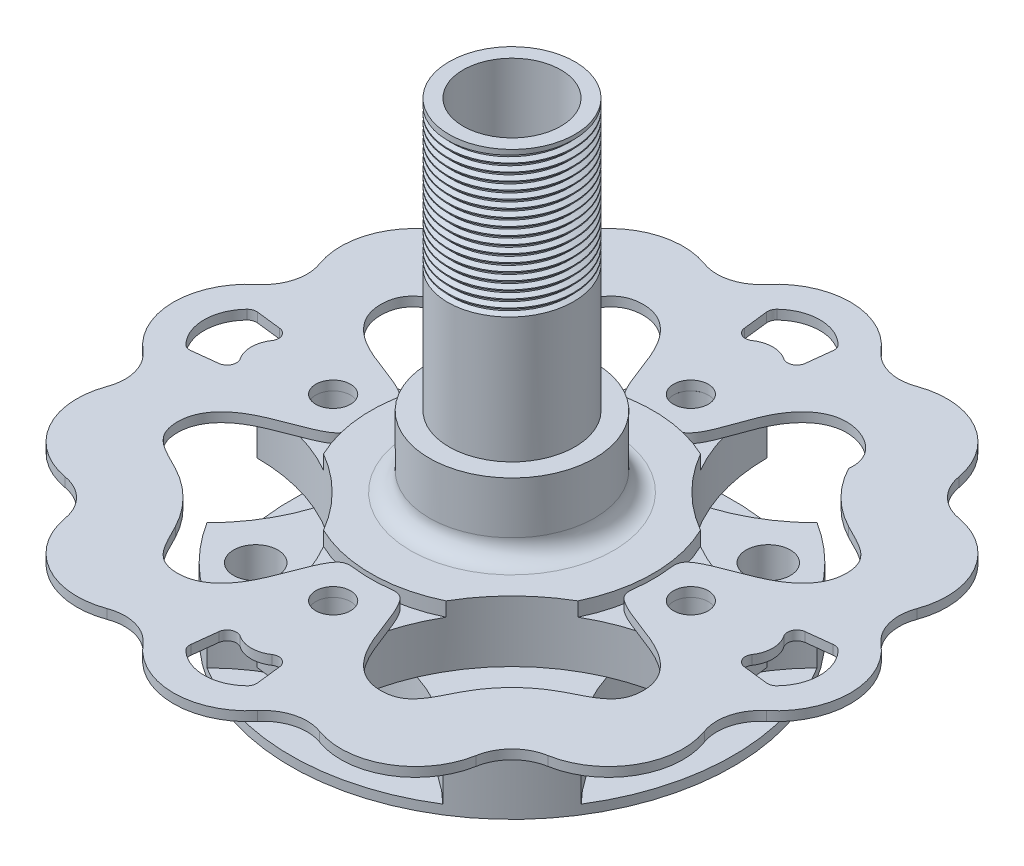
SolidWorks part; units mm, degrees
other "Camera1"
ref_plane "Front Plane" through (0, 0, 0) normal (0, 0, 1) x (1, 0, 0)
ref_plane "Top Plane" through (0, 0, 0) normal (0, 1, 0) x (1, 0, 0)
ref_plane "Right Plane" through (0, 0, 0) normal (1, 0, 0) x (0, 0, -1)
sketch "Sketch1" plane through (0, 0, 0) normal (0, 1, 0) x (1, 0, 0)
  line L0 (-91.3384, 0) -> (0, 0) construction
  line L1 (-79.1014, 45.6692) -> (0, 0) construction
  line L2 (-45.6692, 79.1014) -> (0, 0) construction
  line L3 (0, 91.3384) -> (0, 0) construction
  line L4 (-58.7488, 58.7488) -> (0, 0) construction
  line L5 (-77.6512, 8.9971) -> (-70.888, 8.2135)
  line L9 (0, 91.3384) -> (0, 0) construction
  line L10 (-8.9971, 77.6512) -> (-8.2135, 70.888)
  line L11 (8.9971, 77.6512) -> (8.2135, 70.888)
  line L12 (77.6512, 8.9971) -> (70.888, 8.2135)
  line L13 (0, 91.3384) -> (0, 0) construction
  line L16 (45.6692, 79.1014) -> (0, 0) construction
  line L17 (79.1014, 45.6692) -> (0, 0) construction
  line L18 (91.3384, 0) -> (0, 0) construction
  line L19 (58.7488, 58.7488) -> (0, 0) construction
  line L20 (91.3384, 0) -> (0, 0) construction
  line L23 (0, 91.3384) -> (0, 0) construction
  line L24 (77.6512, -8.9971) -> (70.888, -8.2135)
  line L25 (8.9971, -77.6512) -> (8.2135, -70.888)
  line L26 (-91.3384, 0) -> (0, 0) construction
  line L27 (91.3384, 0) -> (0, 0) construction
  line L28 (77.6512, -8.9971) -> (70.888, -8.2135) [skipped]
  line L30 (-8.9971, -77.6512) -> (-8.2135, -70.888) [skipped]
  line L32 (79.1014, -45.6692) -> (0, 0) construction
  line L33 (45.6692, -79.1014) -> (0, 0) construction
  line L34 (0, -91.3384) -> (0, 0) construction
  line L35 (58.7488, -58.7488) -> (0, 0) construction
  line L36 (0, -91.3384) -> (0, 0) construction
  line L37 (-45.6692, -79.1014) -> (0, 0) construction
  line L38 (-79.1014, -45.6692) -> (0, 0) construction
  line L39 (-58.7488, -58.7488) -> (0, 0) construction
  line L40 (8.9971, 77.6512) -> (8.2135, 70.888) [skipped]
  line L41 (45.6692, 79.1014) -> (0, 0) construction
  line L42 (79.1014, 45.6692) -> (0, 0) construction
  line L43 (58.7488, 58.7488) -> (0, 0) construction
  line L45 (91.3384, 0) -> (0, 0) construction
  line L46 (91.3384, 0) -> (0, 0) construction
  line L47 (79.1014, -45.6692) -> (0, 0) construction
  line L48 (45.6692, -79.1014) -> (0, 0) construction
  line L49 (0, -91.3384) -> (0, 0) construction
  line L50 (58.7488, -58.7488) -> (0, 0) construction
  line L51 (0, -91.3384) -> (0, 0) construction
  line L52 (91.3384, 0) -> (0, 0) construction
  line L53 (-8.9971, -77.6512) -> (-8.2135, -70.888)
  line L54 (-77.6512, -8.9971) -> (-70.888, -8.2135)
  line L55 (0, -91.3384) -> (0, 0) construction
  line L56 (-45.6692, -79.1014) -> (0, 0) construction
  line L57 (-79.1014, -45.6692) -> (0, 0) construction
  line L58 (-91.3384, 0) -> (0, 0) construction
  line L59 (-58.7488, -58.7488) -> (0, 0) construction
  line L60 (-91.3384, 0) -> (0, 0) construction
  line L61 (0, -91.3384) -> (0, 0) construction
  arc A0 (-83.0834, 0) -> (0, 83.0834) centre (0, 0) cw construction
  arc A2 (-91.3384, 0) -> (-84.1072, 15.4663) centre (-71.1829, 0) cw
  arc A3 (-84.1072, 15.4663) -> (-80.5721, 28.6594) centre (-91.7199, 24.5763) ccw
  arc A4 (-80.5721, 28.6594) -> (-65.1058, 55.4478) centre (-61.6462, 35.5915) cw
  arc A5 (-65.1058, 55.4478) -> (-55.4478, 65.1058) centre (-67.1436, 67.1436) ccw
  arc A6 (-55.4478, 65.1058) -> (-28.6594, 80.5721) centre (-35.5915, 61.6462) cw
  arc A7 (-28.6594, 80.5721) -> (-15.4663, 84.1072) centre (-24.5763, 91.7199) ccw
  arc A8 (-15.4663, 84.1072) -> (0, 91.3384) centre (0, 71.1829) cw
  arc A9 (-61.618, 35.4294) -> (-35.4294, 61.618) centre (-67.1436, 67.1436) ccw
  arc A10 (-38.1, 0) -> (-37.7962, 4.8015) centre (0, 0) cw
  arc A11 (-83.0834, 0) -> (-79.7781, 8.2307) centre (-71.1829, 0) cw
  arc A12 (-69.0761, 4.2678) -> (-70.3834, 0) centre (-62.7634, 0) ccw
  arc A14 (-83.0834, 0) -> (-78.8139, 9.1318) centre (-71.1829, 0) cw construction
  arc A15 (-77.6512, 8.9971) -> (-79.7781, 8.2307) centre (-77.9435, 6.474) ccw
  arc A16 (-69.0761, 4.2678) -> (-70.888, 8.2135) centre (-71.1804, 5.6904) ccw
  circle A17 centre (-48.26, 0) radius 4.699
  arc A29 (0, 38.1) -> (-4.8015, 37.7962) centre (0, 0) ccw
  arc A30 (-4.2678, 69.0761) -> (0, 70.3834) centre (0, 62.7634) cw
  arc A36 (-4.2678, 69.0761) -> (-8.2135, 70.888) centre (-5.6904, 71.1804) cw
  arc A41 (-8.9971, 77.6512) -> (-8.2307, 79.7781) centre (-6.474, 77.9435) cw
  arc A42 (0, 83.0834) -> (-8.2307, 79.7781) centre (0, 71.1829) ccw
  arc A50 (0, 91.3384) -> (15.4663, 84.1072) centre (0, 71.1829) cw
  arc A51 (15.4663, 84.1072) -> (28.6594, 80.5721) centre (24.5763, 91.7199) ccw
  arc A57 (28.6594, 80.5721) -> (55.4478, 65.1058) centre (35.5915, 61.6462) cw
  arc A62 (55.4478, 65.1058) -> (65.1058, 55.4478) centre (67.1436, 67.1436) ccw
  arc A63 (65.1058, 55.4478) -> (80.5721, 28.6594) centre (61.6462, 35.5915) cw
  arc A71 (80.5721, 28.6594) -> (84.1072, 15.4663) centre (91.7199, 24.5763) ccw
  arc A72 (84.1072, 15.4663) -> (91.3384, 0) centre (71.1829, 0) cw
  arc A78 (-38.1, 0) -> (-37.7962, -4.8015) centre (0, 0) ccw
  arc A81 (-69.0761, -4.2678) -> (-70.3834, 0) centre (-62.7634, 0) cw
  arc A83 (35.4294, 61.618) -> (61.618, 35.4294) centre (67.1436, 67.1436) ccw
  arc A84 (0, 38.1) -> (4.8015, 37.7962) centre (0, 0) cw
  arc A85 (91.3384, 0) -> (84.1072, -15.4663) centre (71.1829, 0) cw [skipped]
  arc A86 (84.1072, -15.4663) -> (80.5721, -28.6594) centre (91.7199, -24.5763) ccw [skipped]
  arc A87 (80.5721, -28.6594) -> (65.1058, -55.4478) centre (61.6462, -35.5915) cw [skipped]
  arc A88 (65.1058, -55.4478) -> (55.4478, -65.1058) centre (67.1436, -67.1436) ccw [skipped]
  arc A89 (55.4478, -65.1058) -> (28.6594, -80.5721) centre (35.5915, -61.6462) cw [skipped]
  arc A90 (28.6594, -80.5721) -> (15.4663, -84.1072) centre (24.5763, -91.7199) ccw [skipped]
  arc A91 (15.4663, -84.1072) -> (0, -91.3384) centre (0, -71.1829) cw [skipped]
  arc A92 (61.618, -35.4294) -> (35.4294, -61.618) centre (67.1436, -67.1436) ccw [skipped]
  arc A93 (83.0834, 0) -> (79.7781, -8.2307) centre (71.1829, 0) cw [skipped]
  arc A95 (77.6512, -8.9971) -> (79.7781, -8.2307) centre (77.9435, -6.474) ccw [skipped]
  arc A96 (69.0761, -4.2678) -> (70.888, -8.2135) centre (71.1804, -5.6904) ccw [skipped]
  arc A102 (0, -91.3384) -> (-15.4663, -84.1072) centre (0, -71.1829) cw [skipped]
  arc A103 (-15.4663, -84.1072) -> (-28.6594, -80.5721) centre (-24.5763, -91.7199) ccw [skipped]
  arc A104 (-28.6594, -80.5721) -> (-55.4478, -65.1058) centre (-35.5915, -61.6462) cw [skipped]
  arc A105 (-55.4478, -65.1058) -> (-65.1058, -55.4478) centre (-67.1436, -67.1436) ccw [skipped]
  arc A106 (-65.1058, -55.4478) -> (-80.5721, -28.6594) centre (-61.6462, -35.5915) cw [skipped]
  arc A107 (-80.5721, -28.6594) -> (-84.1072, -15.4663) centre (-91.7199, -24.5763) ccw [skipped]
  arc A108 (-84.1072, -15.4663) -> (-91.3384, 0) centre (-71.1829, 0) cw [skipped]
  arc A109 (-35.4294, -61.618) -> (-61.618, -35.4294) centre (-67.1436, -67.1436) ccw [skipped]
  arc A110 (0, -38.1) -> (-4.8015, -37.7962) centre (0, 0) cw [skipped]
  arc A111 (0, -83.0834) -> (-8.2307, -79.7781) centre (0, -71.1829) cw [skipped]
  arc A112 (-4.2678, -69.0761) -> (0, -70.3834) centre (0, -62.7634) ccw [skipped]
  arc A114 (-8.9971, -77.6512) -> (-8.2307, -79.7781) centre (-6.474, -77.9435) ccw [skipped]
  arc A115 (-4.2678, -69.0761) -> (-8.2135, -70.888) centre (-5.6904, -71.1804) ccw [skipped]
  arc A119 (83.0834, 0) -> (0, -83.0834) centre (0, 0) cw construction
  arc A121 (0, -83.0834) -> (-83.0834, 0) centre (0, 0) cw construction
  arc A123 (0, 91.3384) -> (15.4663, 84.1072) centre (0, 71.1829) cw [skipped]
  arc A124 (15.4663, 84.1072) -> (28.6594, 80.5721) centre (24.5763, 91.7199) ccw [skipped]
  arc A125 (28.6594, 80.5721) -> (55.4478, 65.1058) centre (35.5915, 61.6462) cw [skipped]
  arc A126 (55.4478, 65.1058) -> (65.1058, 55.4478) centre (67.1436, 67.1436) ccw [skipped]
  arc A127 (65.1058, 55.4478) -> (80.5721, 28.6594) centre (61.6462, 35.5915) cw [skipped]
  arc A128 (80.5721, 28.6594) -> (84.1072, 15.4663) centre (91.7199, 24.5763) ccw [skipped]
  arc A129 (84.1072, 15.4663) -> (91.3384, 0) centre (71.1829, 0) cw [skipped]
  arc A130 (35.4294, 61.618) -> (61.618, 35.4294) centre (67.1436, 67.1436) ccw [skipped]
  arc A131 (0, 38.1) -> (4.8015, 37.7962) centre (0, 0) cw [skipped]
  arc A132 (0, 83.0834) -> (8.2307, 79.7781) centre (0, 71.1829) cw [skipped]
  arc A133 (4.2678, 69.0761) -> (0, 70.3834) centre (0, 62.7634) ccw [skipped]
  arc A135 (8.9971, 77.6512) -> (8.2307, 79.7781) centre (6.474, 77.9435) ccw [skipped]
  arc A136 (4.2678, 69.0761) -> (8.2135, 70.888) centre (5.6904, 71.1804) ccw [skipped]
  arc A138 (0, 83.0834) -> (83.0834, 0) centre (0, 0) cw construction
  arc A144 (38.1, 0) -> (37.7962, -4.8015) centre (0, 0) cw [skipped]
  arc A145 (69.0761, -4.2678) -> (70.3834, 0) centre (62.7634, 0) ccw [skipped]
  arc A146 (0, 83.0834) -> (8.2307, 79.7781) centre (0, 71.1829) cw
  arc A147 (4.2678, 69.0761) -> (0, 70.3834) centre (0, 62.7634) ccw
  arc A148 (8.9971, 77.6512) -> (8.2307, 79.7781) centre (6.474, 77.9435) ccw
  arc A149 (4.2678, 69.0761) -> (8.2135, 70.888) centre (5.6904, 71.1804) ccw
  circle A150 centre (0, 48.26) radius 4.699
  arc A151 (38.1, 0) -> (37.7962, 4.8015) centre (0, 0) ccw
  arc A152 (69.0761, 4.2678) -> (70.3834, 0) centre (62.7634, 0) cw
  arc A153 (69.0761, 4.2678) -> (70.888, 8.2135) centre (71.1804, 5.6904) cw
  arc A154 (77.6512, 8.9971) -> (79.7781, 8.2307) centre (77.9435, 6.474) cw
  arc A155 (83.0834, 0) -> (79.7781, 8.2307) centre (71.1829, 0) ccw
  arc A156 (0, 38.1) -> (-4.8015, 37.7962) centre (0, 0) ccw
  arc A157 (-4.2678, 69.0761) -> (0, 70.3834) centre (0, 62.7634) cw
  arc A158 (0, 83.0834) -> (83.0834, 0) centre (0, 0) cw construction
  arc A159 (0, 91.3384) -> (91.3384, 0) centre (0, 0) cw construction
  arc A160 (91.3384, 0) -> (84.1072, -15.4663) centre (71.1829, 0) cw
  arc A161 (84.1072, -15.4663) -> (80.5721, -28.6594) centre (91.7199, -24.5763) ccw
  arc A162 (80.5721, -28.6594) -> (65.1058, -55.4478) centre (61.6462, -35.5915) cw
  arc A163 (65.1058, -55.4478) -> (55.4478, -65.1058) centre (67.1436, -67.1436) ccw
  arc A164 (55.4478, -65.1058) -> (28.6594, -80.5721) centre (35.5915, -61.6462) cw
  arc A165 (28.6594, -80.5721) -> (15.4663, -84.1072) centre (24.5763, -91.7199) ccw
  arc A166 (15.4663, -84.1072) -> (0, -91.3384) centre (0, -71.1829) cw
  arc A167 (61.618, -35.4294) -> (35.4294, -61.618) centre (67.1436, -67.1436) ccw
  arc A168 (38.1, 0) -> (37.7962, -4.8015) centre (0, 0) cw
  arc A169 (83.0834, 0) -> (79.7781, -8.2307) centre (71.1829, 0) cw
  arc A170 (69.0761, -4.2678) -> (70.3834, 0) centre (62.7634, 0) ccw
  arc A171 (77.6512, -8.9971) -> (79.7781, -8.2307) centre (77.9435, -6.474) ccw
  arc A172 (69.0761, -4.2678) -> (70.888, -8.2135) centre (71.1804, -5.6904) ccw
  circle A173 centre (48.26, 0) radius 4.699
  arc A174 (0, -38.1) -> (4.8015, -37.7962) centre (0, 0) ccw
  arc A175 (4.2678, -69.0761) -> (0, -70.3834) centre (0, -62.7634) cw
  arc A176 (4.2678, -69.0761) -> (8.2135, -70.888) centre (5.6904, -71.1804) cw
  arc A177 (8.9971, -77.6512) -> (8.2307, -79.7781) centre (6.474, -77.9435) cw
  arc A178 (0, -83.0834) -> (8.2307, -79.7781) centre (0, -71.1829) ccw
  arc A179 (38.1, 0) -> (37.7962, 4.8015) centre (0, 0) ccw
  arc A180 (69.0761, 4.2678) -> (70.3834, 0) centre (62.7634, 0) cw
  arc A181 (83.0834, 0) -> (0, -83.0834) centre (0, 0) cw construction
  arc A182 (91.3384, 0) -> (0, -91.3384) centre (0, 0) cw construction
  arc A183 (0, -91.3384) -> (-15.4663, -84.1072) centre (0, -71.1829) cw
  arc A184 (-15.4663, -84.1072) -> (-28.6594, -80.5721) centre (-24.5763, -91.7199) ccw
  arc A185 (-28.6594, -80.5721) -> (-55.4478, -65.1058) centre (-35.5915, -61.6462) cw
  arc A186 (-55.4478, -65.1058) -> (-65.1058, -55.4478) centre (-67.1436, -67.1436) ccw
  arc A187 (-65.1058, -55.4478) -> (-80.5721, -28.6594) centre (-61.6462, -35.5915) cw
  arc A188 (-80.5721, -28.6594) -> (-84.1072, -15.4663) centre (-91.7199, -24.5763) ccw
  arc A189 (-84.1072, -15.4663) -> (-91.3384, 0) centre (-71.1829, 0) cw
  arc A190 (-35.4294, -61.618) -> (-61.618, -35.4294) centre (-67.1436, -67.1436) ccw
  arc A191 (0, -38.1) -> (-4.8015, -37.7962) centre (0, 0) cw
  arc A192 (0, -83.0834) -> (-8.2307, -79.7781) centre (0, -71.1829) cw
  arc A193 (-4.2678, -69.0761) -> (0, -70.3834) centre (0, -62.7634) ccw
  arc A194 (-8.9971, -77.6512) -> (-8.2307, -79.7781) centre (-6.474, -77.9435) ccw
  arc A195 (-4.2678, -69.0761) -> (-8.2135, -70.888) centre (-5.6904, -71.1804) ccw
  circle A196 centre (0, -48.26) radius 4.699
  arc A197 (-38.1, 0) -> (-37.7962, -4.8015) centre (0, 0) ccw
  arc A198 (-69.0761, -4.2678) -> (-70.3834, 0) centre (-62.7634, 0) cw
  arc A199 (-69.0761, -4.2678) -> (-70.888, -8.2135) centre (-71.1804, -5.6904) cw
  arc A200 (-77.6512, -8.9971) -> (-79.7781, -8.2307) centre (-77.9435, -6.474) cw
  arc A201 (-83.0834, 0) -> (-79.7781, -8.2307) centre (-71.1829, 0) ccw
  arc A202 (0, -38.1) -> (4.8015, -37.7962) centre (0, 0) ccw
  arc A203 (4.2678, -69.0761) -> (0, -70.3834) centre (0, -62.7634) cw
  arc A204 (0, -83.0834) -> (-83.0834, 0) centre (0, 0) cw construction
  arc A205 (0, -91.3384) -> (-91.3384, 0) centre (0, 0) cw construction
  spline S0 degree 3 poles (-52.2384, 38.6101) (-57.1023, 36.0693) (-62.2546, 34.2055) (-63.3566, 23.0387) (-56.4818, 14.6017) (-38.7119, 10.4134) (-37.5569, 6.6856) (-37.7962, 4.8015) knots 0 0 0 0 0.284167 0.347787 0.6362 0.911955 1 1 1 1
  spline S1 degree 3 poles (-38.6101, 52.2384) (-36.0693, 57.1023) (-34.2055, 62.2546) (-23.0387, 63.3566) (-14.6017, 56.4818) (-10.4134, 38.7119) (-6.6856, 37.5569) (-4.8015, 37.7962) knots 0 0 0 0 0.284167 0.347787 0.6362 0.911955 1 1 1 1
  spline S2 degree 3 poles (38.6101, 52.2384) (39.4918, 58.7472) (27.2418, 66.5399) (13.0177, 55.4204) (10.7787, 36.3141) (4.8015, 37.7962) knots 0 0 0 0 0.347787 0.6362 1 1 1 1
  spline S3 degree 3 poles (52.2384, 38.6101) (57.1023, 36.0693) (62.2546, 34.2055) (63.3566, 23.0387) (56.4818, 14.6017) (38.7119, 10.4134) (37.5569, 6.6856) (37.7962, 4.8015) knots 0 0 0 0 0.284167 0.347787 0.6362 0.911955 1 1 1 1
  spline S4 degree 3 poles (52.2384, -38.6101) (57.1023, -36.0693) (62.2546, -34.2055) (63.3566, -23.0387) (56.4818, -14.6017) (38.7119, -10.4134) (37.5569, -6.6856) (37.7962, -4.8015) knots 0 0 0 0 0.284167 0.347787 0.6362 0.911955 1 1 1 1
  spline S5 degree 3 poles (38.6101, -52.2384) (36.0693, -57.1023) (34.2055, -62.2546) (23.0387, -63.3566) (14.6017, -56.4818) (10.4134, -38.7119) (6.6856, -37.5569) (4.8015, -37.7962) knots 0 0 0 0 0.284167 0.347787 0.6362 0.911955 1 1 1 1
  spline S6 degree 3 poles (-38.6101, -52.2384) (-36.0693, -57.1023) (-34.2055, -62.2546) (-23.0387, -63.3566) (-14.6017, -56.4818) (-10.4134, -38.7119) (-6.6856, -37.5569) (-4.8015, -37.7962) knots 0 0 0 0 0.284167 0.347787 0.6362 0.911955 1 1 1 1
  spline S7 degree 3 poles (-52.2384, -38.6101) (-57.1023, -36.0693) (-62.2546, -34.2055) (-63.3566, -23.0387) (-56.4818, -14.6017) (-38.7119, -10.4134) (-37.5569, -6.6856) (-37.7962, -4.8015) knots 0 0 0 0 0.284167 0.347787 0.6362 0.911955 1 1 1 1
  point P26 (0, 0)
  point P27 (-79.1014, 45.6692)
  point P32 (-45.6692, 79.1014)
  point P89 (0, 0)
  point P90 (0, 0)
  point P124 (0, 0)
  point P125 (0, 0)
  point P127 (0, 0)
  point P131 (0, 0)
  point P146 (0, 0)
  point P156 (0, 0)
  point P190 (0, 0)
  point P191 (0, 0)
  point P193 (0, 0)
  point P197 (0, 0)
  point P203 (0, 0)
  point P223 (0, 0)
  point P237 (0, 0)
  point P454 (0, 0)
  point P456 (0, 0)
  point P458 (0, 0)
  point P462 (0, 0)
  point P463 (0, 0)
  dimension "D5" = 10.16
  dimension "D8" = 7.62
  dimension "D11" = 2.54
  dimension "D12" = 2.54
  dimension "D3" = 9.398
  dimension "D7" = 4
  dimension "D4" = 20.32
  dimension "D6" = 8.255
  dimension "D13" = 4
extrude "Boss-Extrude2" add sketch "Sketch1" along normal blind 2.54 contours L10 A8 A7 A6 A5 A4 A3 A2 A11 A15 L5 A16 A12 A81 region at (-87.101, 0, -7.4424)
sketch "Sketch4" plane through (0, 0, 0) normal (0, -1, 0) x (1, 0, 0)
  line L0 (-58.858, 9.9314) -> (-58.858, -9.9314) construction
  line L1 (9.9314, 58.858) -> (-9.9314, 58.858) construction
  line L2 (58.858, -9.9314) -> (58.858, 9.9314) construction
  line L3 (-9.9314, -58.858) -> (9.9314, -58.858) construction
  line L4 (-9.9314, 58.858) -> (-58.858, 58.858) construction
  line L5 (-58.858, 58.858) -> (-58.858, 9.9314) construction
  circle A0 centre (0, 0) radius 59.69
  circle A1 centre (0, 0) radius 38.1 construction
  arc A2 (58.858, 9.9314) -> (9.9314, 58.858) centre (58.858, 58.858) cw
  arc A3 (9.9314, -58.858) -> (58.858, -9.9314) centre (58.858, -58.858) cw
  arc A5 (-9.9314, 58.858) -> (-58.858, 9.9314) centre (-58.858, 58.858) cw
  arc A6 (-58.858, -9.9314) -> (-9.9314, -58.858) centre (-58.858, -58.858) cw
  circle A15 centre (48.26, 0) radius 4.699 construction
  circle A16 centre (0, -48.26) radius 4.699 construction
  circle A17 centre (-48.26, 0) radius 4.699 construction
  circle A18 centre (0, 48.26) radius 4.699 construction
  circle A19 centre (48.26, 0) radius 4.699
  circle A20 centre (0, -48.26) radius 4.699
  circle A21 centre (-48.26, 0) radius 4.699
  circle A22 centre (0, 48.26) radius 4.699
  point P9 (-58.858, 0)
  point P12 (0, 58.858)
  point P19 (0, 0)
  point P31 (0, 0)
  dimension "D1" = 119.38
  dimension "D2" = 19.8628
  dimension "D4" = 90
  dimension "D3" = 4
  dimension "D5" = 4
extrude "Boss-Extrude3" add sketch "Sketch4" along normal blind 12.7 separate body contours A0 A6 A3 A2 A5 A22 A21 A20 A19 region at (0, 0, 0)
sketch "Sketch5" plane through (0, -12.7, 0) normal (0, -1, 0) x (1, 0, 0)
  circle A4 centre (34.574, -34.574) radius 5.969
  circle A5 centre (34.574, 34.574) radius 5.969
  circle A6 centre (-34.574, 34.574) radius 5.969
  circle A7 centre (-34.574, -34.574) radius 5.969
  arc A16 (-50.5004, -31.8215) -> (-31.8215, -50.5004) centre (0, 0) ccw
  arc A17 (31.8215, -50.5004) -> (-31.8215, -50.5004) centre (0, -82.3219) ccw
  arc A18 (31.8215, -50.5004) -> (50.5004, -31.8215) centre (0, 0) ccw
  arc A19 (50.5004, 31.8215) -> (50.5004, -31.8215) centre (82.3219, 0) ccw
  arc A20 (50.5004, 31.8215) -> (31.8215, 50.5004) centre (0, 0) ccw
  arc A21 (-31.8215, 50.5004) -> (31.8215, 50.5004) centre (0, 82.3219) ccw
  arc A22 (-31.8215, 50.5004) -> (-50.5004, 31.8215) centre (0, 0) ccw
  arc A23 (-50.5004, -31.8215) -> (-50.5004, 31.8215) centre (-82.3219, 0) ccw
extrude "Boss-Extrude4" add sketch "Sketch5" along normal blind 15.24
sketch "Sketch6" plane through (0, -27.94, 0) normal (0, -1, 0) x (1, 0, 0)
  circle A0 centre (0, 0) radius 59.69
  circle A1 centre (0, 0) radius 25.4
  arc A2 (58.858, -9.9314) -> (58.858, 9.9314) centre (0, 0) ccw construction
  circle A3 centre (-34.574, -34.574) radius 5.969 construction
  circle A4 centre (34.574, -34.574) radius 5.969 construction
  circle A5 centre (34.574, 34.574) radius 5.969 construction
  circle A6 centre (-34.574, 34.574) radius 5.969 construction
  circle A7 centre (-34.574, -34.574) radius 5.969
  circle A8 centre (34.574, -34.574) radius 5.969
  circle A9 centre (34.574, 34.574) radius 5.969
  circle A10 centre (-34.574, 34.574) radius 5.969
  dimension "D1" = 50.8
extrude "Boss-Extrude5" add sketch "Sketch6" along normal blind 2.54 separate body
sketch "Sketch7" plane through (0, 0, 0) normal (0, 1, 0) x (1, 0, 0)
  circle A0 centre (0, 0) radius 38.1
  arc A1 (-37.7962, 4.8015) -> (-37.7962, -4.8015) centre (0, 0) ccw construction
  arc A11 (-58.858, 9.9314) -> (-9.9314, 58.858) centre (-58.858, 58.858) ccw
  arc A13 (-9.9314, -58.858) -> (-58.858, -9.9314) centre (-58.858, -58.858) ccw
  arc A15 (58.858, -9.9314) -> (9.9314, -58.858) centre (58.858, -58.858) ccw
  arc A17 (9.9314, 58.858) -> (58.858, 9.9314) centre (58.858, 58.858) ccw
  arc A19 (-34.3305, 16.5234) -> (-16.5234, 34.3305) centre (-58.858, 58.858) ccw
  arc A21 (-16.5234, -34.3305) -> (-34.3305, -16.5234) centre (-58.858, -58.858) ccw
  arc A23 (34.3305, -16.5234) -> (16.5234, -34.3305) centre (58.858, -58.858) ccw
  arc A25 (16.5234, 34.3305) -> (34.3305, 16.5234) centre (58.858, 58.858) ccw
  arc A26 (-58.858, 9.9314) -> (-58.858, -9.9314) centre (0, 0) ccw
  arc A27 (-58.858, 9.9314) -> (-58.858, -9.9314) centre (0, 0) ccw
  arc A28 (-9.9314, -58.858) -> (9.9314, -58.858) centre (0, 0) ccw
  arc A29 (-9.9314, -58.858) -> (9.9314, -58.858) centre (0, 0) ccw
  arc A30 (58.858, -9.9314) -> (58.858, 9.9314) centre (0, 0) ccw
  arc A31 (58.858, -9.9314) -> (58.858, 9.9314) centre (0, 0) ccw
  arc A32 (9.9314, 58.858) -> (-9.9314, 58.858) centre (0, 0) ccw
  arc A33 (9.9314, 58.858) -> (-9.9314, 58.858) centre (0, 0) ccw
  arc M20 (-9.9314, 58.858) -> (-58.858, 9.9314) centre (-58.858, 58.858) cw
  arc M24 (-58.858, -9.9314) -> (-9.9314, -58.858) centre (-58.858, -58.858) cw
  arc M28 (9.9314, -58.858) -> (58.858, -9.9314) centre (58.858, -58.858) cw
  arc M32 (58.858, 9.9314) -> (9.9314, 58.858) centre (58.858, 58.858) cw
  dimension "D1" = 0
extrude "Boss-Extrude7" add sketch "Sketch7" along normal blind 3.81 separate body contours A0 M28 M32 M20 M24 region at (0, 0, 0)
sketch "Sketch8" plane through (0, 3.81, 0) normal (0, 1, 0) x (1, 0, 0)
  circle A0 centre (0, 0) radius 22.3012
  dimension "D1" = 44.6024
extrude "Boss-Extrude8" add sketch "Sketch8" along normal blind 19.05
sketch "Sketch9" plane through (0, 22.86, 0) normal (0, 1, 0) x (1, 0, 0)
  circle A0 centre (0, 0) radius 16.9926
  dimension "D1" = 33.9852
extrude "Boss-Extrude9" add sketch "Sketch9" along normal blind 73.025 separate body
sketch "Sketch10" plane through (0, 95.885, 0) normal (0, 1, 0) x (1, 0, 0)
  circle A2 centre (0, 0) radius 13.1826
  circle A3 centre (0, 0) radius 13.1826
  dimension "D1" = 3.81
extrude "Cut-Extrude1" cut sketch "Sketch10" against normal through all both and the other way through all
thread "Thread1" pitch 2.1167 method cut profile "Thread Profile1" start angle 0, offset 0, length 38.1, pitch 2.1167, diameter 33.9852
ref_plane "Plane1" through (-16.9926, 95.885, 0) normal (0, 0, 1) x (-1, 0, 0)
sketch "Thread Profile1" plane through (-16.9926, 95.885, 0) normal (0, 0, 1) x (-1, 0, 0)
  line L0 (0, 0) -> (0, 2.1167) construction
  line L11 (0, 0) -> (0, 1.8521)
  line L12 (0, 1.8521) -> (-1.1457, 1.1906)
  line L13 (-1.1457, 1.1906) -> (-1.1457, 0.6615)
  line L15 (-1.1457, 0.6615) -> (0, 0)
  line L17 (-1.1457, 0.926) -> (0, 0.926) construction
  point P2 (0, 0)
  dimension "Pitch" = 2.1167
  dimension "Profile_Angle" = 60
  dimension "Profile_Land" = 0.5292
  dimension "Profile_Height" = 1.1457
combine bodies "Combine2" operation type add bodies to combine 105 110 111 122 124
fillet "Fillet2" radius 5.08 1 edges at (0, 3.81, 22.3012)
move or copy body "Body-Move/Copy1" [suppressed] bodies to move or copy 105 110 111 112
